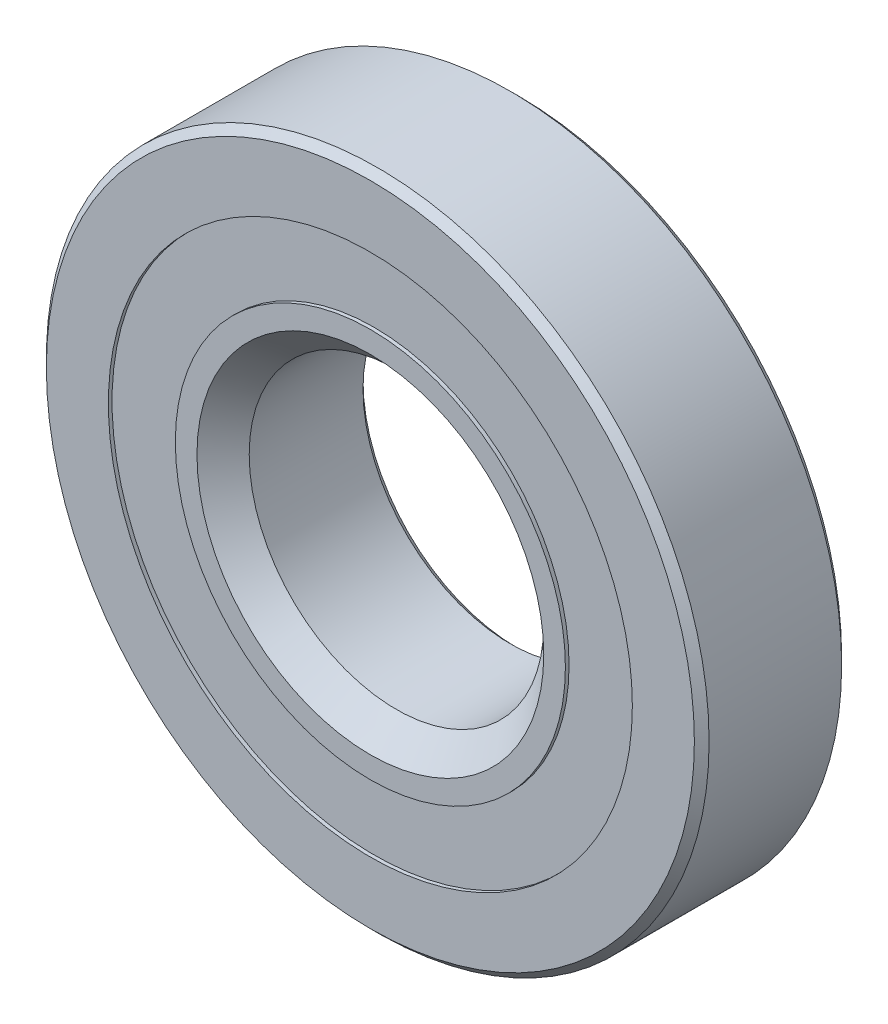
SolidWorks part; units mm, degrees
ref_plane "Front Plane" through (0, 0, 0) normal (0, 0, 1) x (1, 0, 0)
ref_plane "Top Plane" through (0, 0, 0) normal (0, 1, 0) x (1, 0, 0)
ref_plane "Right Plane" through (0, 0, 0) normal (1, 0, 0) x (0, 0, -1)
sketch "Sketch1" plane through (0, 0, 0) normal (1, 0, 0) x (0, 0, -1)
  line L0 (-3.175, 0) -> (3.175, 0) construction
  line L1 (0, 14.2875) -> (0, -14.2875) construction
  line L2 (2.8575, 14.2875) -> (-2.8575, 14.2875)
  line L3 (-2.8575, 14.2875) -> (-3.175, 13.97)
  line L4 (-3.175, 13.97) -> (-3.175, 11.2957)
  line L5 (-3.175, 11.2957) -> (-1.4111, 11.2957)
  line L6 (3.175, 11.2957) -> (1.4111, 11.2957)
  line L7 (3.175, 13.97) -> (3.175, 11.2957)
  line L8 (2.8575, 14.2875) -> (3.175, 13.97)
  line L9 (0, 14.2875) -> (0, 10.3187) construction
  line L10 (0, 10.3187) -> (0, 6.35) construction
  arc A0 (-1.4111, 11.2957) -> (1.4111, 11.2957) centre (0, 10.3187) cw
  point P14 (0, 6.35)
  dimension "Width" = 6.35
  dimension "OD" = 28.575
  dimension "D1" = 45
  dimension "D2" = 0.3175
  dimension "D3" = 2.8222
  dimension "D4" = 0.9769
revolve "Revolve1" add sketch "Sketch1" angle 360 about L0
sketch "Sketch2" plane through (0, 0, 0) normal (1, 0, 0) x (0, 0, -1)
  line L0 (-3.0163, 9.3418) -> (-1.4111, 9.3418)
  line L1 (-3.175, 13.97) -> (-3.175, -13.97) construction
  line L2 (-3.175, 8.409) -> (-3.0163, 8.409) construction
  line L3 (-3.0163, 8.2503) -> (-2.2422, 7.4762)
  line L4 (-2.2422, 7.4762) -> (0, 7.4762)
  line L5 (0, 14.2875) -> (0, -14.2875) construction
  line L6 (0, 7.4762) -> (0, 8.6025)
  line L7 (0, 8.6025) -> (0, 6.35) construction
  line L8 (-3.175, 9.3418) -> (-3.175, 7.4762) construction
  line L9 (-3.175, 7.4762) -> (-2.2422, 7.4762) construction
  line L10 (-3.0163, 9.3418) -> (-3.0163, 8.2503)
  line L11 (-3.0163, 9.3418) -> (-3.0163, 14.1287) construction
  line L12 (-2.8575, 14.2875) -> (-3.175, 13.97) construction
  arc A0 (-1.4111, 9.3418) -> (0, 8.6025) centre (0, 10.3187) ccw
  arc A1 (1.4111, 11.2957) -> (-1.4111, 11.2957) centre (0, 10.3187) ccw construction
  circle A2 centre (0, 10.3187) radius 1.7163 construction
  dimension "D1" = 45
revolve "Revolve2" [suppressed] add sketch "Sketch2" angle 360 about L0
sketch "Sketch3" plane through (0, 0, 0) normal (1, 0, 0) x (0, 0, -1)
  line L0 (-3.0163, 8.2503) -> (-2.2422, 7.4762)
  line L1 (-2.2422, 7.4762) -> (0, 7.4762)
  line L2 (0, 7.4762) -> (0, 8.6025)
  line L3 (-3.175, 8.409) -> (-3.175, 7.4762)
  line L4 (-3.175, 9.3418) -> (-3.175, 7.4762) construction
  line L5 (-3.175, 7.4762) -> (-2.0488, 6.35)
  line L6 (-2.0488, 6.35) -> (2.8575, 6.35)
  line L7 (2.8575, 14.2875) -> (2.8575, -14.2875) construction
  line L8 (2.8575, 6.35) -> (3.175, 6.6675)
  line L9 (3.175, -13.97) -> (3.175, 13.97) construction
  line L10 (3.175, 6.6675) -> (3.175, 9.3418)
  line L11 (3.175, 9.3418) -> (1.4111, 9.3418)
  line L12 (-3.175, 8.409) -> (-3.0163, 8.409)
  line L13 (2.8575, 14.2875) -> (3.175, 13.97) construction
  line L14 (-3.0163, 8.409) -> (-3.0163, 8.2503)
  circle A0 centre (0, 10.3187) radius 1.7163 construction
  arc A1 (1.4111, 9.3418) -> (0, 8.6025) centre (0, 10.3187) cw
revolve "Revolve3" add sketch "Sketch3" angle 360 about L0
sketch "Sketch4" plane through (0, 0, 0) normal (1, 0, 0) x (0, 0, -1)
  line L0 (-1.7163, 10.3187) -> (1.7163, 10.3187)
  circle A1 centre (0, 10.3187) radius 1.7163 construction
  arc A2 (-1.7163, 10.3187) -> (1.7163, 10.3187) centre (0, 10.3187) cw
  arc A3 (1.4111, 11.2957) -> (-1.4111, 11.2957) centre (0, 10.3187) ccw construction
revolve "Revolve4" add sketch "Sketch4" angle 360 about L0
ref_axis "Axis1" through (0, 0, -3.175) along (0, 0, 1)
pattern_circular "CirPattern1" count 12 every 30 about axis through (0, 0, -3.175) along (0, 0, 1) of bodies 104
sketch "Sketch5" plane through (0, 0, 0) normal (1, 0, 0) x (0, 0, -1)
  line L0 (-3.175, 11.2957) -> (-1.4111, 11.2957) construction
  line L1 (-3.0163, 11.2957) -> (-1.7163, 11.2957)
  line L2 (-3.0163, 11.2957) -> (-3.0163, 8.409)
  line L3 (-3.0163, 8.409) -> (-1.7163, 8.409)
  line L4 (-1.7163, 11.2957) -> (-1.7163, 8.409)
  line L6 (-2.8575, 14.2875) -> (-3.175, 13.97) construction
  line L7 (0, 14.2875) -> (0, 6.35) construction
  line L8 (3.0163, 8.409) -> (1.7163, 8.409)
  line L9 (1.7163, 11.2957) -> (1.7163, 8.409)
  line L10 (3.0163, 11.2957) -> (1.7163, 11.2957)
  line L11 (3.0163, 11.2957) -> (3.0163, 8.409)
  circle A0 centre (0, 10.3187) radius 1.7163 construction
  point P10 (-3.0163, 14.1287)
revolve "Revolve5" add sketch "Sketch5" angle 360 about L0
sketch "Sketch6" plane through (0, 0, 0) normal (0, 0, 1) x (1, 0, 0)
  circle A0 centre (0, 0) radius 14.2875 construction
  circle A1 centre (0, 0) radius 14.2875 construction
equation "\"D2@Sketch1\" = \"Width@Sketch1\"*.05"
equation "\"D3@Sketch1\" = \"Width@Sketch1\"/2.25"
equation "\"D4@Sketch1\" = (((\"OD@Sketch1\"-\"Width@Sketch1\")/2)/3.25)/3.5"
equation "\"D2@CirPattern1\" = 360/\"Balls@CirPattern1\""
